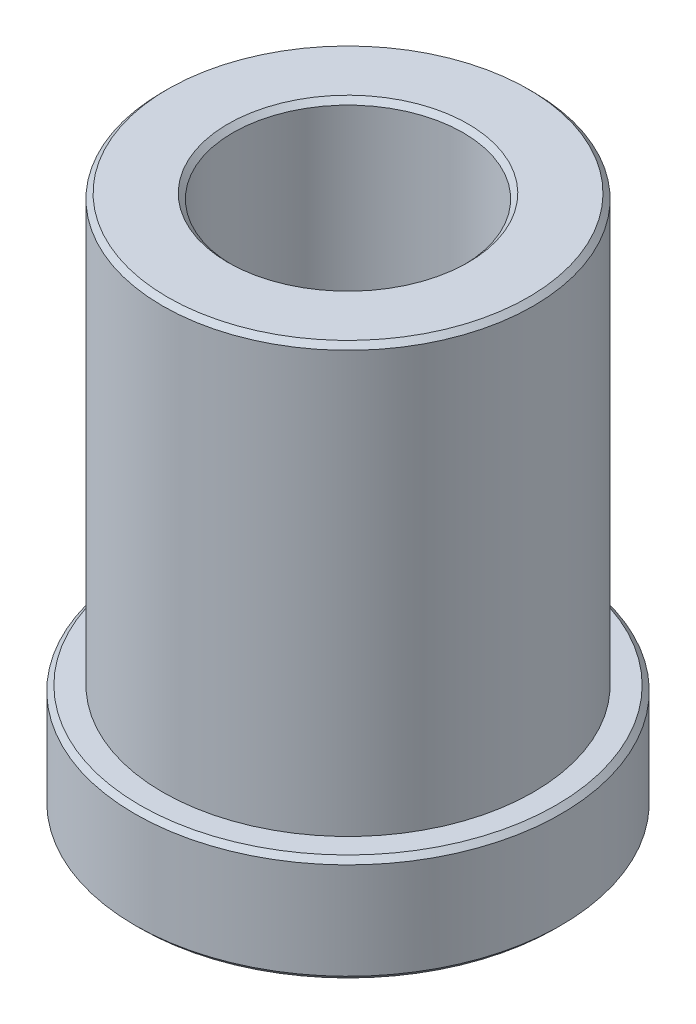
SolidWorks part; units mm, degrees
material "Nylon 101"
ref_plane "Front Plane" through (0, 0, 0) normal (0, 0, 1) x (1, 0, 0)
ref_plane "Top Plane" through (0, 0, 0) normal (0, 1, 0) x (1, 0, 0)
ref_plane "Right Plane" through (0, 0, 0) normal (1, 0, 0) x (0, 0, -1)
sketch "Sketch1" plane through (0, 0, 0) normal (0, 1, 0) x (1, 0, 0)
  circle A0 centre (0, 0) radius 11.049
  dimension "D1" = 22.098
extrude "Boss-Extrude1" add sketch "Sketch1" along normal blind 25.4
sketch "Sketch2" plane through (0, 0, 0) normal (0, -1, 0) x (1, 0, 0)
  circle A0 centre (0, 0) radius 12.7
  dimension "D1" = 25.4
extrude "Boss-Extrude2" add sketch "Sketch2" along normal blind 6.35
sketch "Sketch3" plane through (0, -6.35, 0) normal (0, -1, 0) x (1, 0, 0)
  circle A0 centre (0, 0) radius 6.858
  dimension "D1" = 13.716
extrude "Cut-Extrude1" cut sketch "Sketch3" against normal through all
sketch "Sketch4" plane through (0, -6.35, 0) normal (0, -1, 0) x (1, 0, 0)
  circle A0 centre (0, 0) radius 11.1125
  dimension "D1" = 22.225
ref_plane "Plane1" through (0, 9.525, 0) normal (0, 1, 0) x (1, 0, 0)
chamfer "Chamfer1" distance 0.3 angle 45 5 edges at (0, 0, -12.7) (0, -6.35, -12.7) (0, 25.4, 11.049) (0, 25.4, -6.858) (0, -6.35, -6.858)
equation "\"D1@Chamfer1\"=.3mm"
